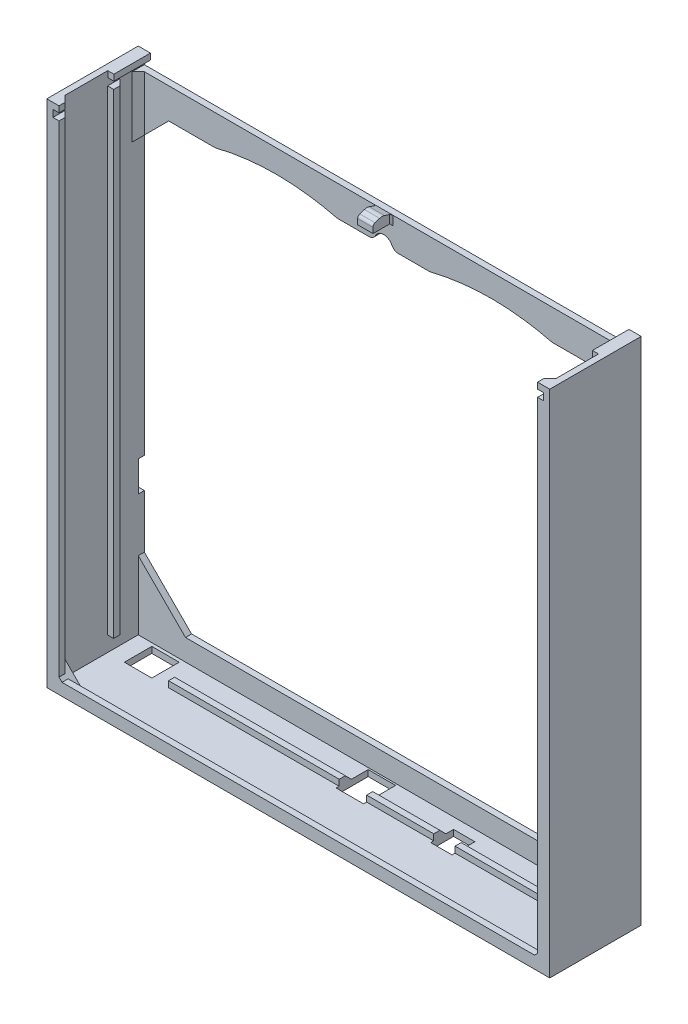
SolidWorks part; units mm, degrees
ref_plane "Front Plane" through (0, 0, 0) normal (0, 0, 1) x (1, 0, 0)
ref_plane "Top Plane" through (0, 0, 0) normal (0, 1, 0) x (1, 0, 0)
ref_plane "Right Plane" through (0, 0, 0) normal (1, 0, 0) x (0, 0, -1)
sketch "Sketch1" plane through (0, 0, 0) normal (0, 0, 1) x (1, 0, 0)
  line L0 (-102.235, 102.235) -> (-104.775, 102.235)
  line L1 (102.235, -102.235) -> (-102.235, -102.235)
  line L2 (102.235, -102.235) -> (102.235, 102.235)
  line L3 (102.235, 102.235) -> (-102.235, 102.235) construction
  line L4 (-102.235, -102.235) -> (-102.235, 102.235)
  line L5 (102.235, -102.235) -> (-102.235, 102.235) construction
  line L6 (102.235, 102.235) -> (-102.235, -102.235) construction
  line L7 (-104.775, 102.235) -> (-104.775, -104.775)
  line L8 (-104.775, -104.775) -> (104.775, -104.775)
  line L9 (104.775, -104.775) -> (104.775, 102.235)
  line L10 (104.775, 102.235) -> (102.235, 102.235)
  point P0 (0, 0)
  dimension "D1" = 204.47
  dimension "D3" = 2.54
  dimension "D4" = 2.54
extrude "Boss-Extrude1" add sketch "Sketch1" along normal blind 35.56
sketch "Sketch2" plane through (0, 0, 35.56) normal (0, 0, 1) x (1, 0, 0)
  line L0 (-102.235, -102.235) -> (-102.235, -95.885)
  line L1 (-102.235, -102.235) -> (-102.235, 102.235) construction
  line L2 (-102.235, -95.885) -> (-95.885, -102.235)
  line L3 (102.235, -102.235) -> (-102.235, -102.235) construction
  line L4 (-95.885, -102.235) -> (-102.235, -102.235)
  line L5 (102.235, -102.235) -> (102.235, -95.885)
  line L6 (102.235, 102.235) -> (102.235, -102.235) construction
  line L7 (102.235, -95.885) -> (95.885, -102.235)
  line L8 (102.235, -102.235) -> (95.885, -102.235)
  dimension "D1" = 6.35
extrude "Boss-Extrude2" add sketch "Sketch2" against normal blind 2.54
sketch "Sketch4" plane through (0, 102.235, 0) normal (0, 1, 0) x (1, 0, 0)
  line L0 (-102.235, -33.02) -> (-99.695, -35.56)
  line L1 (-95.885, -35.56) -> (-102.235, -35.56) construction
  line L2 (-99.695, -35.56) -> (-102.235, -35.56)
  line L3 (-102.235, -35.56) -> (-102.235, -33.02)
  line L4 (102.235, -33.02) -> (99.695, -35.56)
  line L5 (102.235, -35.56) -> (95.885, -35.56) construction
  line L6 (99.695, -35.56) -> (102.235, -35.56)
  line L7 (102.235, -35.56) -> (102.235, -33.02)
  dimension "D1" = 2.54
extrude "Boss-Extrude3" add sketch "Sketch4" against normal up to surface (204.47 mm away) up to face at (0, -102.235, 25.4)
sketch "Sketch5" plane through (-102.235, 0, 0) normal (1, 0, 0) x (0, 0, -1)
  line L0 (-33.02, -102.235) -> (-35.56, -102.235)
  line L3 (-35.56, -102.235) -> (-35.56, -99.695)
  line L4 (-35.56, -99.695) -> (-33.02, -102.235)
  dimension "D1" = 2.54
extrude "Boss-Extrude4" add sketch "Sketch5" along normal up to surface (204.47 mm away) up to face at (102.235, -19.177, 19.812)
sketch "Sketch6" plane through (0, -102.235, 0) normal (0, 1, 0) x (1, 0, 0)
  line L0 (0, -33.02) -> (0, -29.845) construction
  line L1 (95.885, -33.02) -> (-95.885, -33.02) construction
  line L2 (0, -29.845) -> (0, -17.145) construction
  line L3 (0, -17.145) -> (0, -15.9512) construction
  line L4 (0, -15.9512) -> (0, -15.3162) construction
  line L5 (0, -15.3162) -> (-102.235, -15.3162)
  line L6 (-102.235, -33.02) -> (-102.235, 0) construction
  line L7 (-102.235, -15.3162) -> (-102.235, -12.7762)
  line L8 (-102.235, -12.7762) -> (102.235, -12.7762)
  line L9 (102.235, -15.3162) -> (102.235, -12.7762)
  line L10 (0, -15.3162) -> (102.235, -15.3162)
  point P15 (0, -12.7762)
  dimension "D1" = 1.1938
  dimension "D2" = 3.175
  dimension "D3" = 12.7
  dimension "D4" = 0.635
  dimension "D5" = 2.54
extrude "Boss-Extrude5" add sketch "Sketch6" along normal blind 2.54
sketch "Sketch7" plane through (-102.235, 0, 0) normal (1, 0, 0) x (0, 0, -1)
  line L0 (-12.7762, -99.695) -> (-10.2362, -102.235)
  line L1 (-12.7762, -102.235) -> (0, -102.235) construction
  line L2 (-10.2362, -102.235) -> (-12.7762, -102.235)
  line L3 (-12.7762, -102.235) -> (-12.7762, -99.695)
extrude "Boss-Extrude6" add sketch "Sketch7" along normal up to surface (204.47 mm away) up to face at (102.235, -55.5272, 17.2494)
sketch "Sketch8" plane through (0, 102.235, 0) normal (0, 1, 0) x (1, 0, 0)
  line L0 (-102.235, -15.3162) -> (-99.695, -15.3162)
  line L1 (-102.235, -15.3162) -> (102.235, -15.3162) construction
  line L2 (-99.695, -15.3162) -> (-99.695, -12.7762)
  line L3 (102.235, -12.7762) -> (-102.235, -12.7762) construction
  line L4 (-99.695, -12.7762) -> (-102.235, -10.2362)
  line L5 (-102.235, -10.2362) -> (-102.235, -15.3162)
  line L6 (0, 0) -> (0, -61.9382) construction
  line L7 (102.235, 0) -> (-102.235, 0) construction
  line L8 (99.695, -15.3162) -> (99.695, -12.7762)
  line L9 (99.695, -12.7762) -> (102.235, -10.2362)
  line L10 (102.235, -10.2362) -> (102.235, -15.3162)
  line L11 (102.235, -15.3162) -> (99.695, -15.3162)
  dimension "D1" = 2.54
extrude "Boss-Extrude7" add sketch "Sketch8" against normal up to surface (204.47 mm away) up to face at (0, -102.235, 27.1187)
sketch "Sketch9" plane through (0, 0, 35.56) normal (0, 0, 1) x (1, 0, 0)
  line L0 (-104.775, 102.235) -> (-99.695, 102.235)
  line L1 (-99.695, 102.235) -> (-99.695, -98.425)
  line L2 (-99.695, -98.425) -> (-98.425, -99.695)
  line L3 (-98.425, -99.695) -> (98.425, -99.695)
  line L4 (98.425, -99.695) -> (99.695, -98.425)
  line L5 (99.695, -98.425) -> (99.695, 102.235)
  line L6 (99.695, 102.235) -> (104.775, 102.235)
  line L7 (104.775, 102.235) -> (104.775, -104.775)
  line L8 (104.775, -104.775) -> (-104.775, -104.775)
  line L9 (-104.775, 102.235) -> (-104.775, -104.775)
extrude "Boss-Extrude8" add sketch "Sketch9" along normal blind 2.54
sketch "Sketch10" plane through (0, 0, 0) normal (0, 0, -1) x (-1, 0, 0)
  line L0 (-102.235, 102.235) -> (102.235, 102.235)
  line L1 (102.235, 102.235) -> (102.235, 89.535)
  line L2 (102.235, -102.235) -> (102.235, 102.235) construction
  line L3 (102.235, 89.535) -> (-102.235, 89.535) construction
  line L4 (-102.235, -102.235) -> (-102.235, 102.235) construction
  line L5 (-102.235, 89.535) -> (-102.235, 102.235)
  line L6 (-102.235, 89.535) -> (-102.235, 76.835)
  line L7 (-102.235, 102.235) -> (-102.235, -102.235) construction
  line L8 (-102.235, 76.835) -> (-89.535, 89.535)
  line L9 (-89.535, 89.535) -> (89.535, 89.535)
  line L10 (89.535, 89.535) -> (102.235, 76.835)
  line L11 (102.235, 89.535) -> (102.235, 76.835)
  line L12 (-102.235, -102.235) -> (-73.66, -102.235)
  line L13 (-102.235, -102.235) -> (102.235, -102.235) construction
  line L14 (-73.66, -102.235) -> (-102.235, -73.66)
  line L15 (-102.235, -73.66) -> (-102.235, -102.235)
  line L16 (102.235, -102.235) -> (73.66, -102.235)
  line L17 (73.66, -102.235) -> (102.235, -73.66)
  line L18 (102.235, -102.235) -> (102.235, 102.235) construction
  line L19 (102.235, -73.66) -> (102.235, -102.235)
  dimension "D1" = 12.7
  dimension "D2" = 45
  dimension "D3" = 45
  dimension "D4" = 28.575
extrude "Boss-Extrude9" add sketch "Sketch10" against normal blind 2.54
sketch "Sketch11" plane through (0, 0, 0) normal (0, 0, -1) x (-1, 0, 0)
  line L0 (0, 89.535) -> (0, 51.4026) construction
  line L1 (-89.535, 89.535) -> (89.535, 89.535) construction
  line L2 (-89.535, 89.535) -> (0, 89.535) construction
  line L3 (0, 89.535) -> (-44.7675, 95.885) construction
  line L4 (-44.7675, 95.885) -> (-89.535, 89.535) construction
  line L5 (-44.7675, 95.885) -> (-44.7675, 89.535) construction
  line L6 (-44.7675, 89.535) -> (-19.3675, 89.535)
  line L7 (-44.7675, 89.535) -> (-70.1675, 89.535)
  line L8 (-19.3675, 89.535) -> (-44.7675, 95.885) construction
  line L9 (-44.7675, 95.885) -> (-70.1675, 89.535) construction
  line L10 (44.7675, 89.535) -> (19.3675, 89.535)
  line L11 (19.3675, 89.535) -> (44.7675, 95.885) construction
  line L12 (44.7675, 95.885) -> (70.1675, 89.535) construction
  line L13 (44.7675, 89.535) -> (70.1675, 89.535)
  circle A0 centre (0, 89.535) radius 3.81
  spline S0 degree 2 poles (-19.3675, 89.535) (-44.7675, 95.885) (-70.1675, 89.535) knots 0 0 0 1 1 1
  spline S1 degree 2 poles (19.3675, 89.535) (44.7675, 95.885) (70.1675, 89.535) knots 0 0 0 1 1 1
  dimension "D1" = 7.62
  dimension "D2" = 25.4
  dimension "D3" = 25.4
  dimension "D4" = 6.35
extrude "Cut-Extrude1" cut sketch "Sketch11" against normal blind 2.54
fillet "Fillet1" radius 3.175 6 edges at (-70.1675, 89.535, 1.27) (70.1675, 89.535, 1.27) (19.3675, 89.535, 1.27) (-19.3675, 89.535, 1.27) (-3.81, 89.535, 1.27) (3.81, 89.535, 1.27)
chamfer "Chamfer1" distance 2.54 angle 45 2 edges at (102.235, 89.535, 2.54) (-102.235, 89.535, 2.54)
sketch "Sketch12" plane through (0, 102.235, 0) normal (0, 1, 0) x (1, 0, 0)
  line L0 (-99.695, -38.1) -> (-104.775, -38.1) construction
  line L1 (-104.775, 0) -> (-102.235, 0)
  line L2 (-104.775, 0) -> (-104.775, -38.1)
  line L3 (-104.775, -38.1) -> (-102.235, -38.1)
  line L4 (-102.235, 0) -> (-102.235, -38.1)
  line L5 (104.775, -38.1) -> (99.695, -38.1) construction
  line L6 (104.775, 0) -> (102.235, 0)
  line L7 (104.775, 0) -> (104.775, -38.1)
  line L8 (104.775, -38.1) -> (102.235, -38.1)
  line L9 (102.235, 0) -> (102.235, -38.1)
  dimension "D1" = 2.54
  dimension "D2" = 2.54
extrude "Boss-Extrude10" add sketch "Sketch12" along normal blind 5.461
sketch "Sketch13" plane through (0, 0, 38.1) normal (0, 0, 1) x (1, 0, 0)
  line L0 (0, 102.235) -> (0, 67.16) construction
  line L1 (-102.235, 107.696) -> (-99.695, 107.696)
  line L2 (-102.235, 107.696) -> (-102.235, 105.156)
  line L3 (-102.235, 105.156) -> (-99.695, 105.156)
  line L4 (-99.695, 107.696) -> (-99.695, 105.156)
  line L5 (-99.695, 102.235) -> (99.695, 102.235) construction
  line L6 (102.235, 107.696) -> (102.235, 105.156)
  line L7 (102.235, 107.696) -> (99.695, 107.696)
  line L8 (99.695, 107.696) -> (99.695, 105.156)
  line L9 (102.235, 105.156) -> (99.695, 105.156)
  dimension "D1" = 2.54
  dimension "D2" = 2.54
extrude "Boss-Extrude11" add sketch "Sketch13" against normal up to surface (38.1 mm away) up to face at (-2.5029, 53.0196, 0)
sketch "Sketch14" plane through (0, 0, 0) normal (1, 0, 0) x (0, 0, -1)
  line L0 (-2.54, 102.235) -> (-6.35, 102.235) construction
  line L1 (-5.08, 102.235) -> (0, 102.235) construction
  line L3 (-2.54, 102.235) -> (-2.54, 79.375) construction
  line L5 (-10.16, 99.06) -> (-2.54, 99.06)
  line L6 (-2.54, 99.06) -> (-2.54, 102.235)
  line L7 (-6.35, 99.06) -> (-6.35, 103.505) construction
  line L8 (-6.35, 103.505) -> (-2.54, 102.235)
  line L9 (-10.16, 99.06) -> (-10.16, 102.235)
  line L10 (-6.35, 103.505) -> (-10.16, 102.235)
  dimension "D1" = 3.81
  dimension "D2" = 1.27
  dimension "D3" = 0
  dimension "D4" = 3.175
extrude "Boss-Extrude12" add sketch "Sketch14" along normal blind 3.175 and the other way blind 3.175
fillet "Fillet2" radius 3.175 1 edges at (0, 103.505, 6.35)
chamfer "Chamfer2" distance 0.635 angle 45 3 edges at (-3.175, 100.6475, 2.54) (0, 99.06, 2.54) (3.175, 100.6475, 2.54)
fillet "Fillet3" radius 1.27 1 edges at (0, 102.235, 10.16)
sketch "Sketch15" plane through (0, -102.235, 0) normal (0, 1, 0) x (1, 0, 0)
  line L0 (0, 0) -> (0, -8.636) construction
  line L1 (73.66, 0) -> (-73.66, 0) construction
  line L2 (-89.535, 0) -> (-89.535, -7.6581) construction
  line L3 (-102.235, -15.3162) -> (102.235, -15.3162) construction
  line L4 (-83.82, -15.3162) -> (-95.25, -15.3162)
  line L5 (-83.82, -15.3162) -> (-83.82, 0) construction
  line L6 (-83.82, 0) -> (-95.25, 0) construction
  line L7 (-95.25, -15.3162) -> (-95.25, 0) construction
  line L8 (-83.82, -15.3162) -> (-95.25, 0) construction
  line L9 (-83.82, 0) -> (-95.25, -15.3162) construction
  line L15 (-83.82, -15.3162) -> (-83.82, -3.8862)
  line L16 (-83.82, -3.8862) -> (-95.25, -3.8862)
  line L17 (-95.25, -3.8862) -> (-95.25, -15.3162)
  line L18 (-5.715, -10.2362) -> (-5.715, -15.3162)
  line L19 (-104.775, -38.1) -> (-104.775, 0) construction
  line L20 (0, -8.636) -> (0, -10.2362) construction
  line L21 (102.235, -10.2362) -> (-102.235, -10.2362) construction
  line L23 (5.715, -3.2512) -> (-5.715, -3.2512)
  line L24 (5.715, -3.2512) -> (5.715, -10.2362)
  line L26 (-5.715, -3.2512) -> (-5.715, -10.2362)
  line L27 (5.715, -3.2512) -> (-5.715, -10.2362) construction
  line L28 (5.715, -10.2362) -> (-5.715, -3.2512) construction
  line L29 (5.715, -10.2362) -> (5.715, -15.3162)
  line L31 (5.715, -15.3162) -> (5.715, -16.5862)
  line L32 (5.715, -16.5862) -> (-5.715, -16.5862)
  line L33 (-5.715, -15.3162) -> (-5.715, -16.5862)
  point P17 (0, -6.7437)
  dimension "D1" = 11.43
  dimension "D2" = 1.27
  dimension "D3" = 11.43
  dimension "D4" = 9.525
  dimension "D5" = 11.43
  dimension "D6" = 11.43
  dimension "D7" = 11.43
extrude "Cut-Extrude2" cut sketch "Sketch15" against normal blind 3.175 and the other way blind 46.99
sketch "Sketch16" plane through (0, -102.235, 0) normal (0, 1, 0) x (1, 0, 0)
  line L0 (-89.535, -15.3162) -> (-89.535, -3.8862) construction
  line L1 (-5.715, 9.9172) -> (5.715, 9.9172)
  line L2 (-5.715, 9.9172) -> (-5.715, -27.1892)
  line L3 (-5.715, -27.1892) -> (5.715, -27.1892)
  line L4 (5.715, 9.9172) -> (5.715, -27.1892)
  line L5 (-5.715, 9.9172) -> (5.715, -27.1892) construction
  line L6 (-5.715, -27.1892) -> (5.715, 9.9172) construction
  line L7 (-95.25, -15.3162) -> (-83.82, -15.3162) construction
  line L8 (-83.82, -3.8862) -> (-95.25, -3.8862) construction
  line L9 (-89.535, -9.6012) -> (-99.0769, -9.6012) construction
  line L10 (-102.235, -33.02) -> (-102.235, -15.3162) construction
  line L11 (-76.835, -3.4324) -> (-102.235, -3.4324)
  line L12 (-76.835, -3.4324) -> (-76.835, -15.77)
  line L13 (-76.835, -15.77) -> (-102.235, -15.77)
  line L14 (-102.235, -3.4324) -> (-102.235, -15.77)
  line L15 (-76.835, -3.4324) -> (-102.235, -15.77) construction
  line L16 (-76.835, -15.77) -> (-102.235, -3.4324) construction
  point P0 (0, -8.636)
  dimension "D1" = 11.43
extrude "Cut-Extrude3" cut sketch "Sketch16" along normal blind 6.35
sketch "Sketch17" plane through (0, 107.696, 0) normal (0, 1, 0) x (1, 0, 0)
  line L0 (-102.235, -38.1) -> (-102.235, -33.02) construction
  line L1 (-102.235, -33.02) -> (-99.695, -35.56)
  line L2 (-99.695, -35.56) -> (-99.695, -38.1) construction
  line L3 (-99.695, -38.1) -> (-102.235, -38.1) construction
  line L4 (-99.695, -35.56) -> (-99.695, -15.24)
  line L5 (-99.695, 0) -> (-99.695, -38.1) construction
  line L6 (-99.695, -15.24) -> (-102.235, -15.24)
  line L7 (-102.235, -15.24) -> (-102.235, -33.02)
  line L8 (0, 0) -> (0, -67.9912) construction
  line L9 (102.235, 0) -> (-102.235, 0) construction
  line L10 (99.695, -15.24) -> (102.235, -15.24)
  line L11 (99.695, -35.56) -> (99.695, -15.24)
  line L12 (102.235, -33.02) -> (99.695, -35.56)
  line L13 (102.235, -15.24) -> (102.235, -33.02)
  dimension "D1" = 5.08
  dimension "D2" = 2.54
  dimension "D3" = 2.54
  dimension "D4" = 2.54
  dimension "D5" = 20.32
extrude "Cut-Extrude4" cut sketch "Sketch17" against normal up to surface (2.54 mm away) up to face at (100.965, 105.156, 19.05)
sketch "Sketch18" plane through (-102.235, 0, 0) normal (1, 0, 0) x (0, 0, -1)
  line L0 (0, -73.66) -> (0, 76.835) construction
  line L1 (0, -38.735) -> (-2.54, -38.735)
  line L2 (0, -38.735) -> (0, -51.435)
  line L3 (0, -51.435) -> (-2.54, -51.435)
  line L4 (-2.54, -38.735) -> (-2.54, -51.435)
  line L5 (-33.02, -102.235) -> (-2.54, -102.235) construction
  dimension "D1" = 2.54
  dimension "D2" = 50.8
  dimension "D3" = 12.7
extrude "Cut-Extrude5" cut sketch "Sketch18" against normal blind 25.4
sketch "Sketch19" plane through (0, 0, 2.54) normal (0, 0, 1) x (1, 0, 0)
  line L0 (82.55, -93.345) -> (-82.55, -93.345)
  line L1 (73.66, -102.235) -> (102.235, -73.66) construction
  line L2 (-102.235, -73.66) -> (-73.66, -102.235) construction
  line L3 (-82.55, -93.345) -> (-73.66, -102.235)
  line L4 (-73.66, -102.235) -> (73.66, -102.235)
  line L5 (73.66, -102.235) -> (82.55, -93.345)
  line L6 (-104.775, -104.775) -> (104.775, -104.775) construction
  dimension "D1" = 8.89
extrude "Boss-Extrude13" add sketch "Sketch19" against normal up to surface (2.54 mm away) up to face at (-12.891, 47.955, 0)
sketch "Sketch20" plane through (0, -102.235, 0) normal (0, 1, 0) x (1, 0, 0)
  line L0 (0, 0) -> (38.1, 0) construction
  line L1 (38.1, 0) -> (38.1, -15.3162) construction
  line L2 (5.715, -15.3162) -> (102.235, -15.3162) construction
  line L3 (102.235, -10.2362) -> (5.715, -10.2362) construction
  line L4 (33.655, -20.3962) -> (42.545, -20.3962)
  line L5 (33.655, -20.3962) -> (33.655, -10.2362)
  line L6 (33.655, -10.2362) -> (42.545, -10.2362)
  line L7 (42.545, -20.3962) -> (42.545, -10.2362)
  line L8 (33.655, -20.3962) -> (42.545, -10.2362) construction
  line L9 (33.655, -10.2362) -> (42.545, -20.3962) construction
  dimension "D1" = 38.1
  dimension "D2" = 8.89
  dimension "D3" = 0
extrude "Cut-Extrude6" cut sketch "Sketch20" along normal up to surface (2.54 mm away) up to face at (52.705, -99.695, 14.0462)
sketch "Sketch21" plane through (0, -102.235, 0) normal (0, 1, 0) x (1, 0, 0)
  line L0 (-5.715, -16.5862) -> (5.715, -16.5862) construction
  line L1 (33.655, -16.5862) -> (42.545, -16.5862)
  line L2 (33.655, -16.5862) -> (33.655, -7.0612)
  line L3 (33.655, -7.0612) -> (42.545, -7.0612)
  line L4 (42.545, -16.5862) -> (42.545, -7.0612)
  line L5 (5.715, -15.3162) -> (33.655, -15.3162) construction
  dimension "D1" = 0
  dimension "D2" = 8.255
extrude "Cut-Extrude7" cut sketch "Sketch21" against normal blind 7.62
